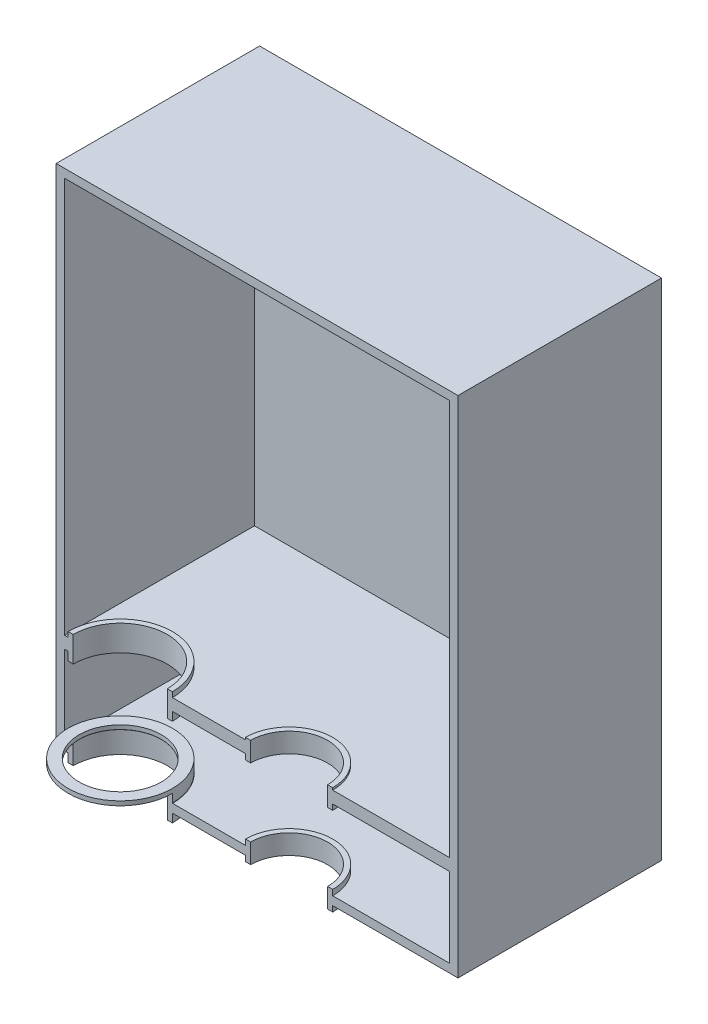
SolidWorks part; units mm, degrees
ref_plane "Front Plane" through (0, 0, 0) normal (0, 0, 1) x (1, 0, 0)
ref_plane "Top Plane" through (0, 0, 0) normal (0, 1, 0) x (1, 0, 0)
ref_plane "Right Plane" through (0, 0, 0) normal (1, 0, 0) x (0, 0, -1)
sketch "Sketch2" plane through (0, 0, 0) normal (0, 0, 1) x (1, 0, 0)
  line L0 (-225, 285) -> (225, 285)
  line L1 (225, 285) -> (225, -178)
  line L2 (225, -285) -> (-225, -285)
  line L3 (-225, -285) -> (-225, -192)
  line L4 (-225, -178) -> (-225, 285)
  line L5 (-225, -192) -> (225, -192)
  line L6 (-225, -178) -> (225, -178)
  line L7 (-235, -295) -> (-235, 295)
  line L8 (-235, 295) -> (235, 295)
  line L9 (235, 295) -> (235, -295)
  line L10 (235, -295) -> (-235, -295)
  line L11 (-225, -285) -> (-225, 285) construction
  line L12 (225, -192) -> (225, -285)
  line L13 (225, 285) -> (225, -285) construction
  point P6 (0, 285)
  dimension "D1" = 570
  dimension "D2" = 450
  dimension "D3" = 93
  dimension "D4" = 14
  dimension "D6" = 10
extrude "Boss-Extrude1" add sketch "Sketch2" along normal blind 222
sketch "Sketch3" plane through (0, 0, 0) normal (0, 0, -1) x (-1, 0, 0)
  line L1 (-235, 295) -> (235, 295)
  line L2 (-235, 295) -> (-235, -295)
  line L3 (-235, -295) -> (235, -295)
  line L4 (235, 295) -> (235, -295)
extrude "Boss-Extrude2" add sketch "Sketch3" along normal blind 16
sketch "Sketch4" plane through (0, -295, 0) normal (0, -1, 0) x (1, 0, 0)
  line L0 (-235, 222) -> (235, 222) construction
  line L2 (-235, 222) -> (-235, -16) construction
  line L3 (235, 222) -> (235, -16) construction
  line L4 (-215, 222) -> (-105, 222)
  line L5 (82.5, 222) -> (-7.5, 222)
  arc A0 (-105, 222) -> (-215, 222) centre (-160, 222) cw
  arc A1 (82.5, 222) -> (-7.5, 222) centre (37.5, 222) cw
  dimension "D1" = 55
  dimension "D2" = 45
  dimension "D3" = 75
  dimension "D4" = 197.5
extrude "Cut-Extrude1" cut sketch "Sketch4" against normal up to surface (117 mm away) up to face at (0, -178, 111)
sketch "Sketch6" plane through (0, 0, 222) normal (0, 0, 1) x (1, 0, 0)
  line L0 (-235, -295) -> (-215, -295) construction
  line L1 (-215, -295) -> (-105, -295) construction
  line L2 (-105, -295) -> (-7.5, -295) construction
  line L3 (-7.5, -295) -> (82.5, -295) construction
  line L4 (82.5, -295) -> (235, -295) construction
  line L5 (235, -295) -> (235, 295) construction
  line L6 (235, 295) -> (-235, 295) construction
  line L7 (-235, 295) -> (-235, -295) construction
  line L8 (-235, -295) -> (-215, -295)
  line L9 (-215, -295) -> (-105, -295)
  line L10 (-105, -295) -> (-7.5, -295)
  line L11 (-7.5, -295) -> (82.5, -295)
  line L12 (82.5, -295) -> (235, -295)
  line L13 (235, -295) -> (235, 295)
  line L14 (235, 295) -> (-235, 295)
  line L15 (-235, 295) -> (-235, -295)
  line L16 (-215, -335) -> (-105, -335)
  line L17 (-105, -335) -> (-7.5, -335)
  line L18 (-7.5, -335) -> (82.5, -335)
  line L19 (82.5, -335) -> (275, -335)
  line L20 (275, -335) -> (275, 335)
  line L21 (275, 335) -> (-275, 335)
  line L22 (-275, 335) -> (-275, -335)
  line L23 (-275, -335) -> (-215, -335)
  dimension "D1" = 40
sketch "Sketch7" plane through (0, -295, 0) normal (0, -1, 0) x (1, 0, 0)
  line L0 (-221, 222) -> (-99, 222)
  line L1 (88.5, 222) -> (-13.5, 222)
  arc A0 (-7.5, 222) -> (82.5, 222) centre (37.5, 222) ccw construction
  arc A1 (-215, 222) -> (-105, 222) centre (-160, 222) ccw construction
  arc A2 (-7.5, 222) -> (82.5, 222) centre (37.5, 222) ccw
  arc A3 (-215, 222) -> (-105, 222) centre (-160, 222) ccw
  arc A4 (-221, 222) -> (-99, 222) centre (-160, 222) ccw
  arc A5 (-13.5, 222) -> (88.5, 222) centre (37.5, 222) ccw
  line M1 (-7.5, 222) -> (-105, 222)
  arc M2 (-105, 222) -> (-215, 222) centre (-160, 222) cw
  line M3 (-215, 222) -> (-235, 222)
  line M7 (235, 222) -> (82.5, 222)
  arc M8 (82.5, 222) -> (-7.5, 222) centre (37.5, 222) cw
  dimension "D1" = 6
extrude "Cut-Extrude2" cut sketch "Sketch7" along direction (0, 1, 0) on the side against the normal up to surface (117 mm away) contours A4 M3 M1 M2 | A5 M1 M7 M8
sketch "Sketch8" plane through (0, -295, 0) normal (0, -1, 0) x (1, 0, 0)
  line L1 (-215, 222) -> (-221, 222)
  line L2 (-99, 222) -> (-105, 222)
  line L5 (-225, 0) -> (225, 0)
  line L6 (225, 0) -> (225, 222)
  line L7 (225, 222) -> (-225, 222)
  line L8 (-225, 222) -> (-225, 0)
  line L9 (-225, 0) -> (225, 0)
  line L10 (225, 0) -> (225, 222)
  line L11 (225, 222) -> (-225, 222)
  line L12 (-225, 222) -> (-225, 0)
  arc A0 (-221, 222) -> (-99, 222) centre (-160, 222) ccw construction
  arc A2 (-221, 222) -> (-99, 222) centre (-160, 222) ccw
  arc A4 (-215, 222) -> (-105, 222) centre (-160, 222) ccw
  arc M6 (-99, 222) -> (-221, 222) centre (-160, 222) cw
  dimension "D1" = 0
  dimension "D2" = 6
extrude "Boss-Extrude4" add sketch "Sketch8" against normal mid plane 30 from offset 5 contours A4 L1 L2 M6 offset against normal yes
sketch "Sketch9" plane through (0, -295, 0) normal (0, -1, 0) x (1, 0, 0)
  line L0 (-7.5, 222) -> (-13.5, 222)
  line L1 (88.5, 222) -> (82.5, 222)
  arc A0 (-13.5, 222) -> (88.5, 222) centre (37.5, 222) ccw construction
  arc A1 (-13.5, 222) -> (88.5, 222) centre (37.5, 222) ccw
  arc A2 (-7.5, 222) -> (82.5, 222) centre (37.5, 222) ccw
  dimension "D1" = 6
extrude "Boss-Extrude5" add sketch "Sketch9" along normal mid plane 23 from offset 5 offset against normal yes
ref_plane "Plane1" through (0, -238.5, 0) normal (0, -1, 0) x (-1, 0, 0)
ref_plane "Plane2" through (0, -238.5, 0) normal (0, -1, 0) x (-1, 0, 0)
mirror "Mirror2" about plane through (0, -238.5, 0) normal (0, -1, 0) of "Boss-Extrude5", "Boss-Extrude4"
sketch "Sketch11" plane through (0, 0, 222) normal (0, 0, 1) x (1, 0, 0)
  line L0 (-99, -275) -> (-99, -270)
  line L1 (-99, -270) -> (-112, -270)
  line L2 (-112, -270) -> (-112, -275)
  line L3 (-105, -275) -> (-215, -275) construction
  line L4 (-112, -275) -> (-99, -275)
  line L5 (-215, -290) -> (-105, -290) construction
  line L6 (-215, -275) -> (-215, -305) construction
  line L7 (-105, -275) -> (-105, -305) construction
  line L8 (-160, -290) -> (-160, -262.3121) construction
  dimension "D1" = 5
  dimension "D2" = 13
revolve "Revolve2" add sketch "Sketch11" angle 360 about L8
fillet "Fillet1" radius 0.3 1 edges at (-160, -285, 161)
fillet "Fillet2" radius 0.3 1 edges at (-160, -275, 174)
fillet "Fillet3" radius 0.3 1 edges at (-160, -275, 167)
